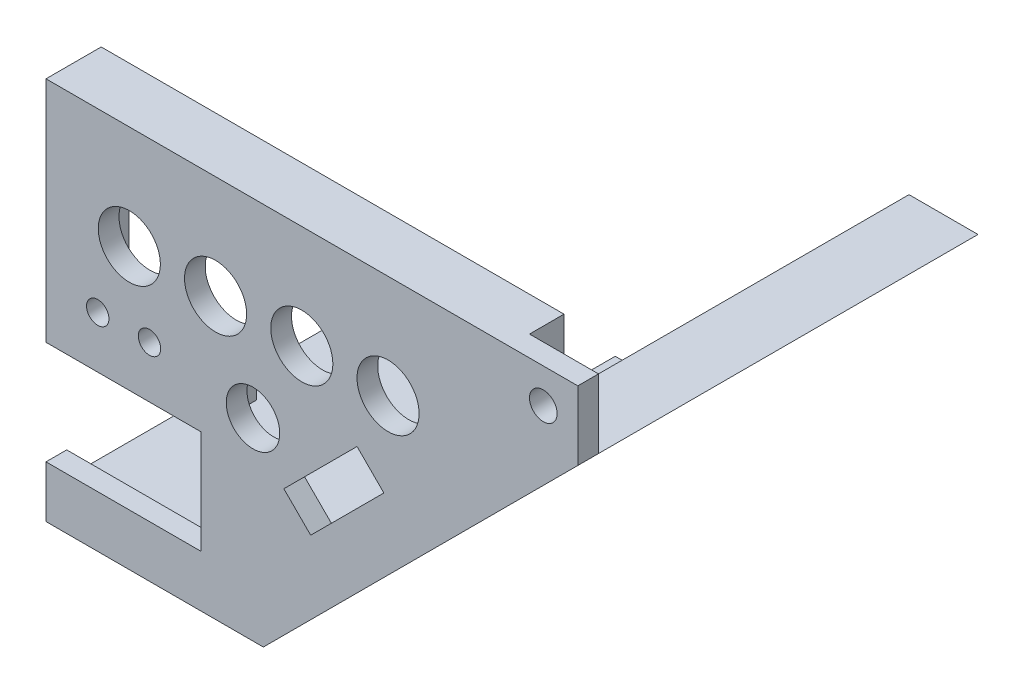
SolidWorks part; units mm, degrees
ref_plane "Plan de face" through (0, 0, 0) normal (0, 0, 1) x (1, 0, 0)
ref_plane "Plan de dessus" through (0, 0, 0) normal (0, 1, 0) x (1, 0, 0)
ref_plane "Plan de droite" through (0, 0, 0) normal (1, 0, 0) x (0, 0, -1)
sketch "Main-Sketch" plane through (0, 0, 0) normal (0, 0, 1) x (1, 0, 0)
  line L0 (0, 0) -> (63, 0)
  line L1 (63, 0) -> (154.15, 91.15)
  line L2 (154.15, 91.15) -> (154.15, 111.15)
  line L3 (0, 111.15) -> (0, 0)
  line L4 (154.15, 111.15) -> (0, 111.15)
  dimension "D1" = 135
  dimension "D2" = 154.15
  dimension "D3" = 63
  dimension "D4" = 20
  dimension "D5" = 128.9056
extrude "Main-Extrusion" add sketch "Main-Sketch" along normal blind 6
sketch "MainHole-Sketch" plane through (0, 0, 6) normal (0, 0, 1) x (1, 0, 0)
  line L0 (0, 0) -> (63, 0) construction
  line L2 (154.15, 91.15) -> (154.15, 111.15) construction
  line L3 (68.9454, 42.715) -> (76.7236, 34.9368)
  line L4 (76.7236, 34.9368) -> (97.9368, 56.15)
  line L5 (97.9368, 56.15) -> (90.1586, 63.9282)
  line L6 (90.1586, 63.9282) -> (68.9454, 42.715)
  line L7 (63, 0) -> (154.15, 91.15) construction
  line L9 (154.15, 111.15) -> (0, 111.15) construction
  line L10 (0, 111.15) -> (0, 0) construction
  line L11 (0, 111.15) -> (0, 0) construction
  circle A0 centre (49.15, 81.15) radius 9
  circle A1 centre (74.15, 81.15) radius 9
  circle A2 centre (99.15, 81.15) radius 9
  circle A3 centre (24.15, 81.15) radius 9
  circle A4 centre (60, 56) radius 7.75
  circle A5 centre (30, 60) radius 3.25
  circle A6 centre (15, 60) radius 3.25
  point P14 (154.15, 101.15)
  dimension "D1" = 18
  dimension "D4" = 25
  dimension "D11" = 15.5
  dimension "D5" = 6.5
  dimension "D2" = 25
  dimension "D3" = 25
  dimension "D6" = 55
  dimension "D7" = 11
  dimension "D8" = 30
  dimension "D9" = 15
  dimension "D10" = 55
  dimension "D12" = 56
  dimension "D13" = 60
  dimension "D14" = 30
  dimension "D15" = 30
  dimension "D16" = 60
  dimension "D17" = 15
extrude "MainHole" cut sketch "MainHole-Sketch" against normal through all
sketch "Vertical-Fix-Hole-Sketch" plane through (0, 0, 6) normal (0, 0, 1) x (1, 0, 0)
  line L0 (154.15, 91.15) -> (154.15, 111.15) construction
  line L1 (154.15, 111.15) -> (0, 111.15) construction
  circle A0 centre (144.15, 101.15) radius 4
  dimension "D3" = 8
  dimension "D1" = 10
  dimension "D2" = 10
extrude "Vertical-Fix-Hole" cut sketch "Vertical-Fix-Hole-Sketch" against normal through all
sketch "MotherBoard-Vertical-Hole-Sketch" plane through (0, 0, 6) normal (0, 0, 1) x (1, 0, 0)
  line L0 (0, 111.15) -> (0, 0) construction
  line L1 (0, 45) -> (45, 45)
  line L2 (0, 45) -> (0, 15)
  line L3 (0, 15) -> (45, 15)
  line L4 (45, 45) -> (45, 15)
  line L5 (0, 0) -> (63, 0) construction
  dimension "D1" = 45
  dimension "D2" = 45
  dimension "D3" = 30
extrude "MotherBoard-Vertical-Hole" cut sketch "MotherBoard-Vertical-Hole-Sketch" against normal through all
sketch "Front-Vertical-Sketch" plane through (0, 0, 0) normal (0, 0, -1) x (-1, 0, 0)
  line L0 (-154.15, 91.15) -> (-134.15, 91.15)
  line L1 (-138.4931, 86.8069) -> (-59.6863, 8)
  line L2 (-59.6863, 8) -> (0, 8)
  line L3 (0, 15) -> (0, 0) construction
  line L4 (0, 8) -> (0, 0)
  line L5 (0, 0) -> (-63, 0)
  line L6 (-63, 0) -> (-154.15, 91.15) construction
  line L7 (0, 0) -> (-63, 0) construction
  line L8 (-63, 0) -> (-154.15, 91.15)
  line L9 (-134.15, 91.15) -> (-138.4931, 86.8069)
  dimension "D1" = 8
  dimension "D2" = 8
  dimension "D3" = 20
extrude "Front-Vertical-Extrusion" add sketch "Front-Vertical-Sketch" along normal blind 110
sketch "Reinforcement-Sketch" plane through (0, 0, 0) normal (0, 0, -1) x (-1, 0, 0)
  line L0 (-8, 51) -> (-45, 51)
  line L1 (-138.4931, 86.8069) -> (-134.15, 91.15) construction
  line L2 (-8, 51) -> (-8, 105.15)
  line L3 (-8, 105.15) -> (-128.15, 105.15)
  line L4 (-134.15, 111.15) -> (0, 111.15)
  line L5 (-154.15, 111.15) -> (0, 111.15) construction
  line L6 (0, 111.15) -> (0, 45)
  line L7 (-128.15, 76.4637) -> (-138.4931, 86.8069)
  line L8 (-59.6863, 8) -> (-138.4931, 86.8069) construction
  line L9 (-59.6863, 8) -> (-138.4931, 86.8069) construction
  line L10 (-138.4931, 86.8069) -> (-134.15, 91.15)
  line L11 (-128.15, 105.15) -> (-128.15, 76.4637)
  line L13 (-134.15, 91.15) -> (-134.15, 111.15)
  line L14 (-45, 51) -> (-45, 45)
  line L15 (-45, 45) -> (0, 45)
  line L16 (-45, 15) -> (-45, 45) construction
  dimension "D1" = 6
  dimension "D2" = 8
  dimension "D4" = 6
  dimension "D5" = 6
extrude "Reinforcement-Extrusion" add sketch "Reinforcement-Sketch" along normal blind 10
sketch "Right-Screw-Sketch" plane through (0, 0, 0) normal (-1, 0, 0) x (0, 0, 1)
  line L0 (-10, 45) -> (-10, 111.15) construction
  line L1 (6, 111.15) -> (-10, 111.15) construction
  circle A0 centre (-5, 101.15) radius 1.35
  dimension "D1" = 2.7
  dimension "D2" = 5
  dimension "D3" = 10
extrude "Right-Screw-Hole" cut sketch "Right-Screw-Sketch" against normal up to next
pattern_linear "Screw-Linear-Repetition" count 3 spacing 20 along (0, -1, 0) of "Right-Screw-Hole"
sketch "Right-Fix-Sketch" plane through (0, 0, 0) normal (-1, 0, 0) x (0, 0, 1)
  line L0 (6, 111.15) -> (-10, 111.15) construction
  line L1 (6, 111.15) -> (6, 45) construction
  line L2 (6, 0) -> (-110, 0) construction
  line L4 (0, 15) -> (0, 8) construction
  circle A0 centre (0, 91.15) radius 3
  circle A1 centre (0, 71.15) radius 3
  circle A2 centre (0, 51.15) radius 3
  circle A3 centre (-40, 4) radius 3
  circle A4 centre (0, 4) radius 3
  circle A5 centre (-80, 4) radius 3
  dimension "D2" = 6
  dimension "D8" = 40
  dimension "D1" = 20
  dimension "D3" = 20
  dimension "D4" = 20
  dimension "D5" = 6
  dimension "D6" = 4
  dimension "D7" = 40
extrude "Right-Fix-Extrusion" cut sketch "Right-Fix-Sketch" against normal up to surface (8 mm away) up to face at (8, 81.15, -3.65)
sketch "LcdHole-Sketch" plane through (0, 0, 0) normal (0, -1, 0) x (1, 0, 0)
  line L0 (0, 6) -> (63, 6) construction
  line L1 (0, -110) -> (49, -110)
  line L2 (0, -110) -> (0, -89)
  line L3 (0, -89) -> (49, -89)
  line L4 (49, -110) -> (49, -89)
  dimension "D1" = 95
  dimension "D2" = 49
extrude "LcdHole" cut sketch "LcdHole-Sketch" against normal through all
sketch "Lcd-Fix-Sketch" plane through (0, 8, 0) normal (0, -1, 0) x (-1, 0, 0)
  line L0 (-49, 110) -> (-49, 89) construction
  line L4 (-49, 89) -> (0, 89) construction
  circle A0 centre (-46.5, 83) radius 1.35
  dimension "D3" = 2.5
  dimension "D1" = 2.7
  dimension "D2" = 6
extrude "Lcd-Fix" cut sketch "Lcd-Fix-Sketch" along normal blind 7
hole_wizard "Fraisage pour vis à tête fraisée M32" positions "Esquisse3" profile "Esquisse4" countersink size "M3" standard "Ansi Metric" end condition up to next
sketch "Esquisse3" plane through (0, 0, 0) normal (0, -1, 0) x (-1, 0, 0)
  line L0 (0, -6) -> (-63, -6) construction
  line L1 (0, -6) -> (0, 89) construction
  point P0 (-52, 72)
  dimension "D1" = 78
  dimension "D2" = 52
sketch "Esquisse4" plane through (52, 0, -72) normal (1, 0, 0) x (0, 0, -1)
  line L0 (0, 0) -> (0, 8)
  line L1 (0, 8) -> (1.7, 8)
  line L2 (1.7, 8) -> (1.7, 1.45)
  line L3 (1.7, 1.45) -> (3.15, 0)
  line L5 (3.15, 0) -> (0, 0)
  line L6 (-1.7, 1.45) -> (-3.15, 0) construction
  line L11 (0, -6.35) -> (0, 107.95) construction
  dimension "Diamètre du perçage jusqu'au prochain" = 3.4
  dimension "Profondeur du perçage jusqu'au prochain" = 8
  dimension "Diamètre du fraisage entrant" = 6.3
  dimension "Angle du fraisage entrant" = 90
pattern_linear "MotherBoard-Fix-Linear-Repetition" count 2 spacing 66 along (0, 0, 1) of "Fraisage pour vis à tête fraisée M32"
sketch "PowerBoard-Hole-Sketch" plane through (31.5, -31.5, 0) normal (0.7071, -0.7071, 0) x (0, 0, -1)
  line L0 (110, 173.4533) -> (110, 44.5477) construction
  line L1 (37, 67.5477) -> (95, 67.5477)
  line L2 (37, 67.5477) -> (37, 141.4533)
  line L3 (37, 141.4533) -> (95, 141.4533)
  line L4 (95, 67.5477) -> (95, 141.4533)
  line L5 (-6, 44.5477) -> (-6, 173.4533) construction
  line L6 (-6, 44.5477) -> (110, 44.5477) construction
  line L8 (110, 173.4533) -> (0, 173.4533) construction
  dimension "D1" = 15
  dimension "D2" = 43
  dimension "D3" = 23
  dimension "D4" = 32
extrude "PowerBoard-Hole" cut sketch "PowerBoard-Hole-Sketch" against normal up to next
sketch "PowerBoard-Window-Sketch" plane through (31.5, -31.5, 0) normal (0.7071, -0.7071, 0) x (0, 0, -1)
  line L0 (37, 141.4533) -> (37, 67.5477) construction
  line L1 (31, 61.5477) -> (101, 61.5477)
  line L2 (31, 61.5477) -> (31, 147.4533)
  line L3 (31, 147.4533) -> (101, 147.4533)
  line L4 (101, 61.5477) -> (101, 147.4533)
  line L5 (37, 67.5477) -> (95, 67.5477) construction
  line L6 (95, 67.5477) -> (95, 141.4533) construction
  line L7 (95, 141.4533) -> (37, 141.4533) construction
  dimension "D1" = 6
  dimension "D2" = 6
  dimension "D3" = 6
  dimension "D4" = 6
extrude "PowerBoard-Window" cut sketch "PowerBoard-Window-Sketch" against normal blind 5
sketch "PowerBoard-Window-Fix-Sketch" plane through (27.9645, -27.9645, 0) normal (0.7071, -0.7071, 0) x (0, 0, -1)
  line L0 (31, 147.4533) -> (31, 61.5477) construction
  line L1 (37, 141.4533) -> (37, 67.5477) construction
  line L3 (31, 61.5477) -> (101, 61.5477) construction
  line L4 (37, 67.5477) -> (95, 67.5477) construction
  line L6 (95, 67.5477) -> (95, 141.4533) construction
  line L7 (95, 141.4533) -> (37, 141.4533) construction
  circle A0 centre (34, 104.5005) radius 1.25
  circle A1 centre (66, 64.5477) radius 1.25
  circle A2 centre (98, 104.5005) radius 1.25
  circle A3 centre (66, 144.4533) radius 1.25
  point P10 (31, 104.5005)
  point P13 (37, 104.5005)
  point P18 (66, 61.5477)
  point P19 (66, 67.5477)
  dimension "D1" = 2.5
  dimension "D2" = 3
  dimension "D3" = 3
  dimension "D4" = 3
  dimension "D5" = 3
extrude "PowerBoard-Window-Fix" cut sketch "PowerBoard-Window-Fix-Sketch" against normal through all
sketch "PowerBoard-Fix-Sketch" plane through (25.8431, -25.8431, 0) normal (-0.7071, 0.7071, 0) x (0, 0, 1)
  line L0 (-110, 159.3112) -> (-10, 159.3112) construction
  line L1 (0, 47.8614) -> (0, 144.6837) construction
  circle A0 centre (-32, 137.3112) radius 4
  circle A1 centre (-31, 68.8112) radius 3
  dimension "D1" = 8
  dimension "D2" = 6
  dimension "D3" = 68.5
  dimension "D4" = 1
  dimension "D5" = 22
  dimension "D6" = 32
extrude "PowerBoard-Fix" add sketch "PowerBoard-Fix-Sketch" along normal blind 5
sketch "PowerBoard-Fix-Hole-Sketch" plane through (22.3076, -22.3076, 0) normal (-0.7071, 0.7071, 0) x (0, 0, 1)
  circle A0 centre (-32, 137.3112) radius 1.25
  circle A1 centre (-31, 68.8112) radius 1.25
  dimension "D1" = 2.5
  dimension "D2" = 2.5
extrude "PowerBoard-Fix-Hole" cut sketch "PowerBoard-Fix-Hole-Sketch" against normal blind 7
sketch "Esquisse5" plane through (0, 0, -110) normal (0, 0, -1) x (-1, 0, 0)
  line L0 (-138.4931, 86.8069) -> (-134.15, 91.15)
  line L1 (-138.4931, 86.8069) -> (-134.15, 91.15) construction
  line L2 (-59.6863, 8) -> (-138.4931, 86.8069) construction
  line L3 (-134.15, 91.15) -> (-127.0789, 84.0789)
  line L4 (-127.0789, 84.0789) -> (-131.4221, 79.7358)
  line L5 (-131.4221, 79.7358) -> (-138.4931, 86.8069)
  dimension "D1" = 10
extrude "Boss.-Extru.1" add sketch "Esquisse5" against normal blind 10
sketch "Esquisse6" plane through (0, 0, -110) normal (0, 0, -1) x (-1, 0, 0)
  line L0 (-131.4221, 79.7358) -> (-127.0789, 84.0789) construction
  line L2 (-127.0789, 84.0789) -> (-134.15, 91.15) construction
  circle A0 centre (-132.7853, 85.4436) radius 1.35
  dimension "D1" = 2.7
  dimension "D2" = 5
  dimension "D3" = 3.07
extrude "Enlèv. mat.-Extru.1" cut sketch "Esquisse6" against normal up to next
